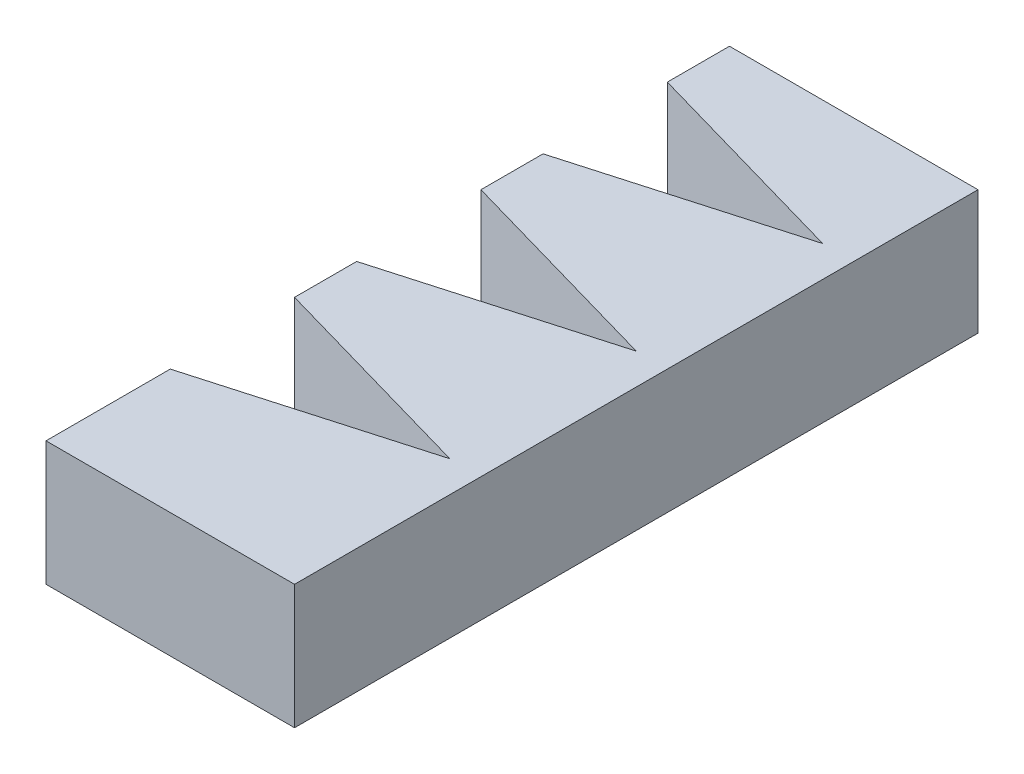
SolidWorks part; units mm, degrees
ref_plane "Front Plane" through (0, 0, 0) normal (0, 0, 1) x (1, 0, 0)
ref_plane "Top Plane" through (0, 0, 0) normal (0, 1, 0) x (1, 0, 0)
ref_plane "Right Plane" through (0, 0, 0) normal (1, 0, 0) x (0, 0, -1)
ref_axis "Axis2" through (0, 0, -126) along (0, 0, 1)
sketch "Sketch1" plane through (0, 0, 0) normal (0, 1, 0) x (1, 0, 0)
  line L0 (0, 100) -> (0, 110)
  line L1 (0, 0) -> (40, 0)
  line L2 (0, 0) -> (0, 20)
  line L4 (40, 0) -> (40, 110)
  line L6 (0, 20) -> (35, 30)
  line L7 (35, 30) -> (0, 40)
  line L8 (0, 50) -> (35, 60)
  line L9 (35, 60) -> (0, 70)
  line L10 (0, 80) -> (35, 90)
  line L11 (35, 90) -> (0, 100)
  line L12 (0, 110) -> (35, 110)
  line L13 (35, 110) -> (40, 110)
  line L14 (0, 70) -> (0, 80)
  line L15 (0, 40) -> (0, 50)
  point P1 (-70.5311, 102.4619)
  point P2 (0, 0)
  point P6 (0, 0)
  point P7 (0, 0)
  point P8 (0, 0)
  point P9 (0, 20)
  point P10 (0, 0)
  point P11 (0, 40)
  point P12 (0, 50)
  point P13 (0, 0)
  point P14 (0, 70)
  point P15 (0, 80)
  point P16 (0, 0)
  point P17 (0, 0)
  point P18 (0, 100)
  point P19 (0, 110)
  point P20 (0, 0)
  point P21 (0, 0)
  point P23 (0, 0)
  point P24 (0, 0)
  point P35 (0, 0)
  point P37 (0, 0)
  point P38 (0, 0)
  point P39 (0, 0)
  point P40 (0, 0)
  point P41 (0, 0)
  point P42 (0, 0)
  point P43 (0, 0)
  point P44 (0, 0)
  point P45 (0, 0)
  point P46 (0, 0)
  dimension "D2" = 40
extrude "Boss-Extrude1" add sketch "Sketch1" along normal blind 20
